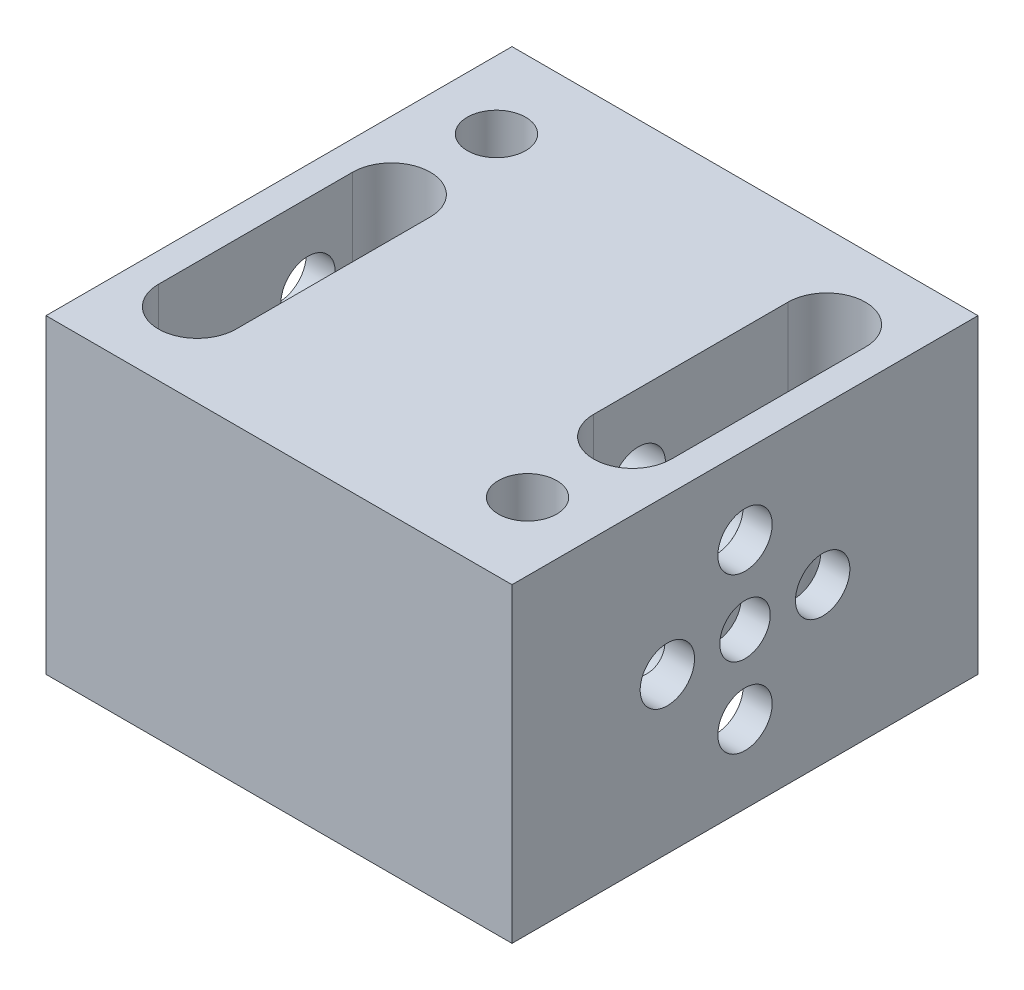
SolidWorks part; units mm, degrees
ref_plane "前视基准面" through (0, 0, 0) normal (0, 0, 1) x (1, 0, 0)
ref_plane "上视基准面" through (0, 0, 0) normal (0, 1, 0) x (1, 0, 0)
ref_plane "右视基准面" through (0, 0, 0) normal (1, 0, 0) x (0, 0, -1)
sketch "草图1" plane through (0, 0, 0) normal (1, 0, 0) x (0, 0, -1)
  line L1 (0, 0) -> (76.2, 0)
  line L2 (0, 0) -> (0, 50.8)
  line L3 (0, 50.8) -> (76.2, 50.8)
  line L4 (76.2, 0) -> (76.2, 50.8)
  circle A0 centre (38.1, 25.4) radius 4.1275
  circle A1 centre (25.4, 25.4) radius 4.445
  circle A2 centre (50.8, 25.4) radius 4.445
  circle A3 centre (38.1, 38.1) radius 4.445
  circle A4 centre (38.1, 12.7) radius 4.445
  point P15 (0, 0)
  point P16 (0, 0)
  point P17 (0, 0)
  point P18 (0, 0)
  point P19 (0, 0)
  point P20 (0, 0)
  point P21 (0, 0)
  point P22 (0, 0)
  point P23 (0, 0)
  point P24 (0, 0)
  dimension "D2" = 12.7
  dimension "D9" = 8.255
  dimension "D10" = 8.89
  dimension "D11" = 8.89
  dimension "D12" = 8.89
  dimension "D13" = 8.89
  dimension "D1" = 76.2
  dimension "D3" = 12.7
  dimension "D4" = 12.7
  dimension "D5" = 12.7
  dimension "D6" = 25.4
  dimension "D7" = 50.8
  dimension "D8" = 38.1
sketch "草图2" plane through (0, 0, 0) normal (1, 0, 0) x (0, 0, -1)
extrude "凸台-拉伸1" add sketch "草图1" along normal blind 76.2
sketch "草图3" plane through (0, 0, 0) normal (0, 1, 0) x (1, 0, 0)
  line L0 (11.0998, 45.3898) -> (11.0998, 13.6398) construction
  line L1 (0, 0) -> (76.2, 0)
  line L2 (0, 0) -> (0, 76.2)
  line L3 (0, 76.2) -> (76.2, 76.2)
  line L4 (76.2, 0) -> (76.2, 76.2)
  line L5 (17.4498, 45.3898) -> (17.4498, 13.6398)
  line L6 (4.7498, 45.3898) -> (4.7498, 13.6398)
  line L7 (65.1002, 30.8102) -> (65.1002, 62.5602) construction
  line L8 (58.7502, 30.8102) -> (58.7502, 62.5602)
  line L9 (71.4502, 30.8102) -> (71.4502, 62.5602)
  circle A0 centre (11.0998, 62.5602) radius 4.7625
  circle A1 centre (65.1002, 13.6398) radius 4.7625
  arc A2 (17.4498, 45.3898) -> (4.7498, 45.3898) centre (11.0998, 45.3898) ccw
  arc A3 (4.7498, 13.6398) -> (17.4498, 13.6398) centre (11.0998, 13.6398) ccw
  arc A4 (58.7502, 30.8102) -> (71.4502, 30.8102) centre (65.1002, 30.8102) ccw
  arc A5 (71.4502, 62.5602) -> (58.7502, 62.5602) centre (65.1002, 62.5602) ccw
  point P11 (11.0998, 29.5148)
  point P16 (65.1002, 46.6852)
  point P23 (0, 0)
  point P24 (0, 0)
  point P25 (0, 0)
  point P26 (0, 0)
  dimension "D5" = 9.525
  dimension "D8" = 9.525
  dimension "D9" = 6.35
  dimension "D10" = 31.75
  dimension "D11" = 6.35
  dimension "D1" = 76.2
  dimension "D2" = 76.2
  dimension "D3" = 11.0998
  dimension "D4" = 13.6398
  dimension "D6" = 13.6398
  dimension "D7" = 11.0998
  dimension "D12" = 31.75
extrude "凸台-拉伸2" add sketch "草图3" along normal blind 50.8
extrude "切除-拉伸2" cut sketch "草图1<4>" along normal blind 76.2 contours A3 | A1 | A4 | A0 | A2
sketch "草图1<4>" plane through (0, 0, 0) normal (1, 0, 0) x (0, 0, -1) same geometry as "草图1"
sketch "草图9" plane through (0, 0, 0) normal (0, 1, 0) x (1, 0, 0)
  line L4 (0, 76.2) -> (0, 0)
  line L5 (0, 0) -> (76.2, 0)
  line L6 (76.2, 0) -> (76.2, 76.2)
  line L7 (76.2, 76.2) -> (0, 76.2)
  line L8 (0, 76.2) -> (0, 0)
  line L9 (0, 0) -> (76.2, 0)
  line L10 (76.2, 0) -> (76.2, 76.2)
  line L11 (76.2, 76.2) -> (0, 76.2)
  dimension "D1" = 0
sketch "草图10" plane through (0, 0, 0) normal (0, 1, 0) x (1, 0, 0)
  line L0 (11.0998, 13.6398) -> (11.0998, 45.3898) construction
  line L1 (4.7498, 13.6398) -> (4.7498, 45.3898)
  line L2 (17.4498, 13.6398) -> (17.4498, 45.3898)
  line L3 (65.1002, 62.5602) -> (65.1002, 30.8102) construction
  line L4 (71.4502, 62.5602) -> (71.4502, 30.8102)
  line L5 (58.7502, 62.5602) -> (58.7502, 30.8102)
  circle A0 centre (11.0998, 62.5602) radius 4.7625
  circle A1 centre (65.1002, 13.6398) radius 4.7625
  arc A2 (4.7498, 13.6398) -> (17.4498, 13.6398) centre (11.0998, 13.6398) ccw
  arc A3 (17.4498, 45.3898) -> (4.7498, 45.3898) centre (11.0998, 45.3898) ccw
  arc A4 (71.4502, 62.5602) -> (58.7502, 62.5602) centre (65.1002, 62.5602) ccw
  arc A5 (58.7502, 30.8102) -> (71.4502, 30.8102) centre (65.1002, 30.8102) ccw
  point P6 (11.0998, 29.5148)
  point P11 (65.1002, 46.6852)
  point P18 (0, 0)
  point P19 (0, 0)
  point P22 (0, 0)
  point P23 (0, 0)
  dimension "D5" = 6.35
  dimension "D6" = 6.35
  dimension "D8" = 9.525
  dimension "D10" = 9.525
  dimension "D1" = 11.0998
  dimension "D2" = 11.0998
  dimension "D3" = 31.75
  dimension "D4" = 31.75
  dimension "D7" = 13.6398
  dimension "D9" = 13.6398
extrude "切除-拉伸3" cut sketch "草图10" along normal blind 50.8
